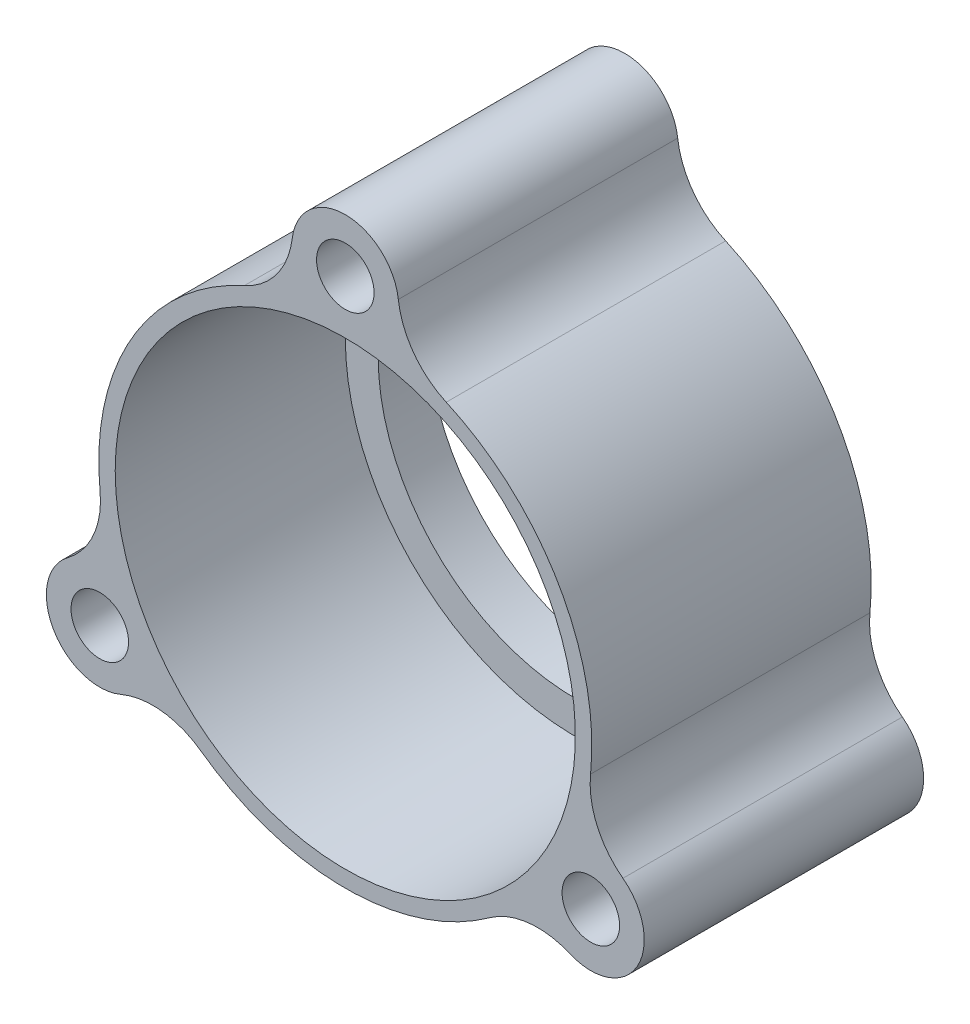
SolidWorks part; units mm, degrees
ref_plane "Front Plane" through (0, 0, 0) normal (0, 0, 1) x (1, 0, 0)
ref_plane "Top Plane" through (0, 0, 0) normal (0, 1, 0) x (1, 0, 0)
ref_plane "Right Plane" through (0, 0, 0) normal (1, 0, 0) x (0, 0, -1)
sketch "Sketch1" plane through (0, 0, 0) normal (0, 0, 1) x (1, 0, 0)
  circle A0 centre (0, 0) radius 15
  dimension "D1" = 30
extrude "Boss-Extrude1" add sketch "Sketch1" along normal blind 14
sketch "Sketch4" plane through (0, 0, 0) normal (0, 0, -1) x (-1, 0, 0)
  circle A0 centre (0, 0) radius 14
  dimension "D1" = 28
extrude "Cut-Extrude1" cut sketch "Sketch4" against normal through all
sketch "Sketch3" plane through (0, 0, 0) normal (0, 0, -1) x (-1, 0, 0)
  circle A0 centre (0, 0) radius 15
  circle A1 centre (0, 0) radius 12
  circle A2 centre (0, 0) radius 15 construction
  dimension "D1" = 24
extrude "Boss-Extrude2" add sketch "Sketch3" along normal blind 3
sketch "Sketch6" plane through (0, 0, 14) normal (0, 0, 1) x (1, 0, 0)
  line L0 (0, 17.25) -> (0, 0) construction
  circle A0 centre (0, 17.25) radius 3.25
  circle A1 centre (0, 17.25) radius 1.75
  dimension "D1" = 6.5
  dimension "D2" = 3.5
  dimension "D3" = 17.25
extrude "Boss-Extrude4" add sketch "Sketch6" against normal up to surface (17 mm away) up to face at (-15, 0, -3)
fillet "Fillet1" radius 5 2 edges at (2.1811, 14.8406, 5.5) (-2.1811, 14.8406, 5.5)
ref_axis "Axis2" through (0, 0, 14) along (0, 0, -1)
pattern_circular "CirPattern2" count 3 every 120 about axis through (0, 0, 14) along (0, 0, -1) of "Fillet1", "Boss-Extrude4"
